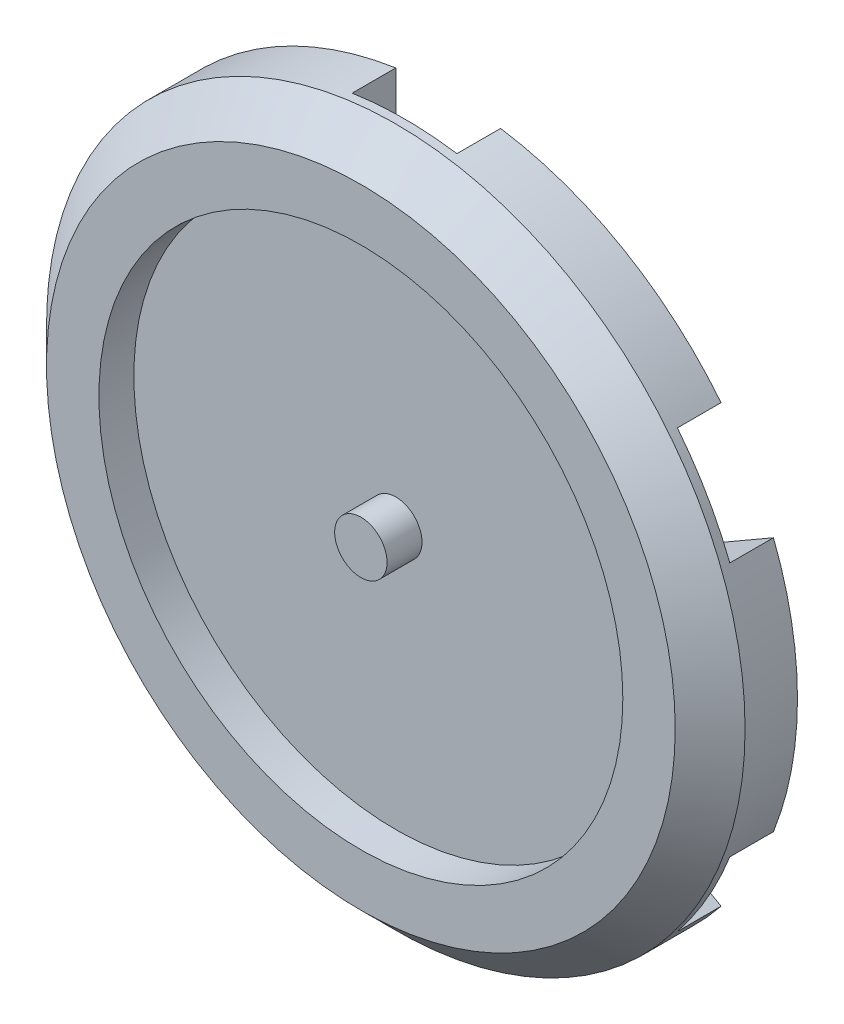
SolidWorks part; units mm, degrees
ref_plane "Front Plane" through (0, 0, 0) normal (1, 0, 0) x (0, 1, 0)
ref_plane "Top Plane" through (0, 0, 0) normal (0, 0, 1) x (0, 1, 0)
ref_plane "Right Plane" through (0, 0, 0) normal (0, 1, 0) x (-1, 0, 0)
sketch "Sketch1" plane through (0, 0, 0) normal (0, 0, 1) x (0, 1, 0)
  circle A0 centre (0, 0) radius 75
  circle A1 centre (0, 0) radius 100
  dimension "D1" = 150
  dimension "D2" = 200
extrude "Boss-Extrude1" add sketch "Sketch1" along normal blind 25 contours A0 | A1 A0 region at (0, 0, 0) region at (0, -97.1716, 0)
extrude "Cut-Extrude1" cut sketch "Sketch1<3>" against normal blind 10 from surface contours A0 region at (0, 0, 0) starting at face at (100, 0, 25)
sketch "Sketch1<3>" plane through (0, 0, 0) normal (0, 0, 1) x (0, 1, 0) same geometry as "Sketch1"
chamfer "Chamfer1" distance 10 angle 45 1 edges at (100, 0, 25)
sketch "Sketch3" plane through (0, 0, 0) normal (0, 0, -1) x (1, 0, 0)
  line L0 (0, 0) -> (0, 100) construction
  line L3 (-15, 98.8686) -> (-15, 68.8686)
  line L4 (-15, 68.8686) -> (15, 68.8686)
  line L5 (15, 98.8686) -> (15, 68.8686)
  circle A0 centre (0, 0) radius 100 construction
  arc A1 (15, 98.8686) -> (-15, 98.8686) centre (0, 0) ccw
  point P10 (0, 68.8686)
  dimension "D1" = 30
  dimension "D2" = 30
extrude "Cut-Extrude2" cut sketch "Sketch3" against normal blind 12.5
pattern_circular "CirPattern1" count 6 over 360 about axis through (0, 0, 0) along (0, 0, 1) of "Cut-Extrude2"
sketch "Sketch4" plane through (0, 0, 15) normal (0, 0, 1) x (1, 0, 0)
  circle A0 centre (0, 0) radius 7.5
  dimension "D1" = 15
extrude "Boss-Extrude2" add sketch "Sketch4" along normal blind 10
